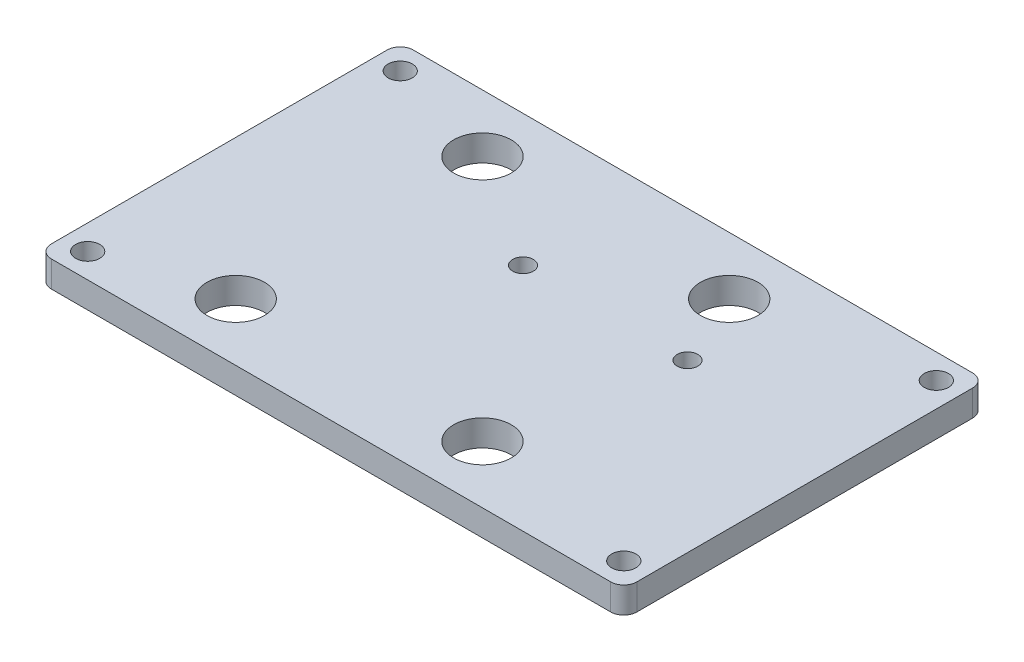
SolidWorks part; units mm, degrees
material "AISI 4130 Steel, annealed at 865C"
ref_plane "Front Plane" through (0, 0, 0) normal (0, 0, 1) x (1, 0, 0)
ref_plane "Top Plane" through (0, 0, 0) normal (0, 1, 0) x (1, 0, 0)
ref_plane "Right Plane" through (0, 0, 0) normal (1, 0, 0) x (0, 0, -1)
sketch "Sketch1" plane through (0, 0, 0) normal (0, 1, 0) x (1, 0, 0)
  line L0 (7, -7) -> (7, -37) construction
  line L1 (0, 0) -> (44, 0)
  line L2 (0, 0) -> (0, -44)
  line L3 (0, -44) -> (44, -44)
  line L4 (44, 0) -> (44, -44)
  line L5 (37, -7) -> (7, -7) construction
  line L6 (20.93, -16) -> (40.93, -16) construction
  line L7 (22, 0) -> (22, -44) construction
  line L8 (44, 0) -> (51.18, 0)
  line L9 (51.18, 0) -> (51.18, -44)
  line L10 (51.18, -44) -> (44, -44)
  line L11 (22, -22) -> (-15.2405, -22) construction
  circle A0 centre (7, -7) radius 3.5
  circle A1 centre (37, -7) radius 3.5
  circle A2 centre (37, -37) radius 3.5
  circle A3 centre (7, -37) radius 3.5
  circle A4 centre (20.93, -16) radius 0.5
  circle A5 centre (40.93, -16) radius 0.5
  dimension "D1" = 7
  dimension "D2" = 1
  dimension "D3" = 30
  dimension "D4" = 30
  dimension "D5" = 20
  dimension "D6" = 44
  dimension "D7" = 44
  dimension "D8" = 7
  dimension "D9" = 7
  dimension "D10" = 1.07
  dimension "D11" = 7.18
  dimension "D12" = 6
extrude "Boss-Extrude1" add sketch "Sketch1" along normal blind 3.175 contours L4 L1 L2 L3 A5 A4 A3 A2 A1 A0 | L10 L9 L8 L4 region at (21.9921, 0, 22.0053) region at (47.59, 0, 22)
sketch "Sketch3" plane through (0, 3.175, 0) normal (0, 1, 0) x (1, 0, 0)
  line L1 (0, 0) -> (-10, 0)
  line L2 (0, 0) -> (0, -44)
  line L3 (0, -44) -> (-10, -44)
  line L4 (-10, 0) -> (-10, -44)
  line L5 (51.18, 0) -> (61.18, 0)
  line L6 (51.18, 0) -> (51.18, -44)
  line L7 (51.18, -44) -> (61.18, -44)
  line L8 (61.18, 0) -> (61.18, -44)
  circle A0 centre (-7, -3) radius 1.4732
  circle A1 centre (-7, -41) radius 1.4732
  circle A2 centre (58.18, -41) radius 1.4732
  circle A3 centre (58.18, -3) radius 1.4732
  point P10 (-7, -41)
  point P12 (58.18, -41)
  point P14 (-7, -3)
  point P15 (58.18, -3)
  point P27 (-7, -41)
  dimension "D6" = 2.9464
  dimension "D1" = 10
  dimension "D2" = 3
  dimension "D3" = 3
  dimension "D4" = 3
  dimension "D5" = 3
extrude "Boss-Extrude2" add sketch "Sketch3" against normal up to surface (3.175 mm away) up to face at (40.93, 0, 16.5)
hole_wizard "M3x0.5 Tapped Hole1" positions "3DSketch1" profile "Sketch2" tap size "M3x0.5" standard "ANSI Metric" end condition through all
sketch3d "3DSketch1"
  circle A2 centre (40.93, 3.175, 16) radius 0.5 construction
  circle A3 centre (20.93, 3.175, 16) radius 0.5 construction
  point P0 (40.93, 3.175, 16)
  point P2 (20.93, 3.175, 16)
  point P17 (40.93, 3.675, 16)
  point P25 (20.93, 3.675, 16)
sketch "Sketch2" plane through (40.93, 3.175, 16) normal (1, 0, 0) x (0, 0, 1)
  line L0 (0, 0) -> (0, 3.175)
  line L1 (0, 3.175) -> (1.25, 3.175)
  line L2 (1.25, 3.175) -> (1.25, 0)
  line L5 (1.25, 0) -> (0, 0)
  line L11 (0, -6.35) -> (0, 107.95) construction
  dimension "Thru Tap Drill Dia." = 2.5
  dimension "Thru Tap Drill Depth" = 3.175
cosmetic thread "Hole Thread9" parameters "D2"=3
cosmetic thread "Hole Thread10" parameters "D2"=3
fillet "Fillet1" radius 1.5875 4 edges at (61.18, 1.5875, 0) (61.18, 1.5875, 44) (-10, 1.5875, 44) (-10, 1.5875, 0)
equation "\"D8@Sketch1\"=(\"D7@Sketch1\"-\"D4@Sketch1\")/2"
equation "\"D9@Sketch1\"=\"D8@Sketch1\""
equation "\"D10@Sketch1\"=9.37mm-6.3-2-0.14+0.58-0.44"
equation "\"D3@Sketch3\"=\"D2@Sketch3\""
equation "\"D4@Sketch3\"=\"D3@Sketch3\""
equation "\"D5@Sketch3\"=\"D2@Sketch3\""
